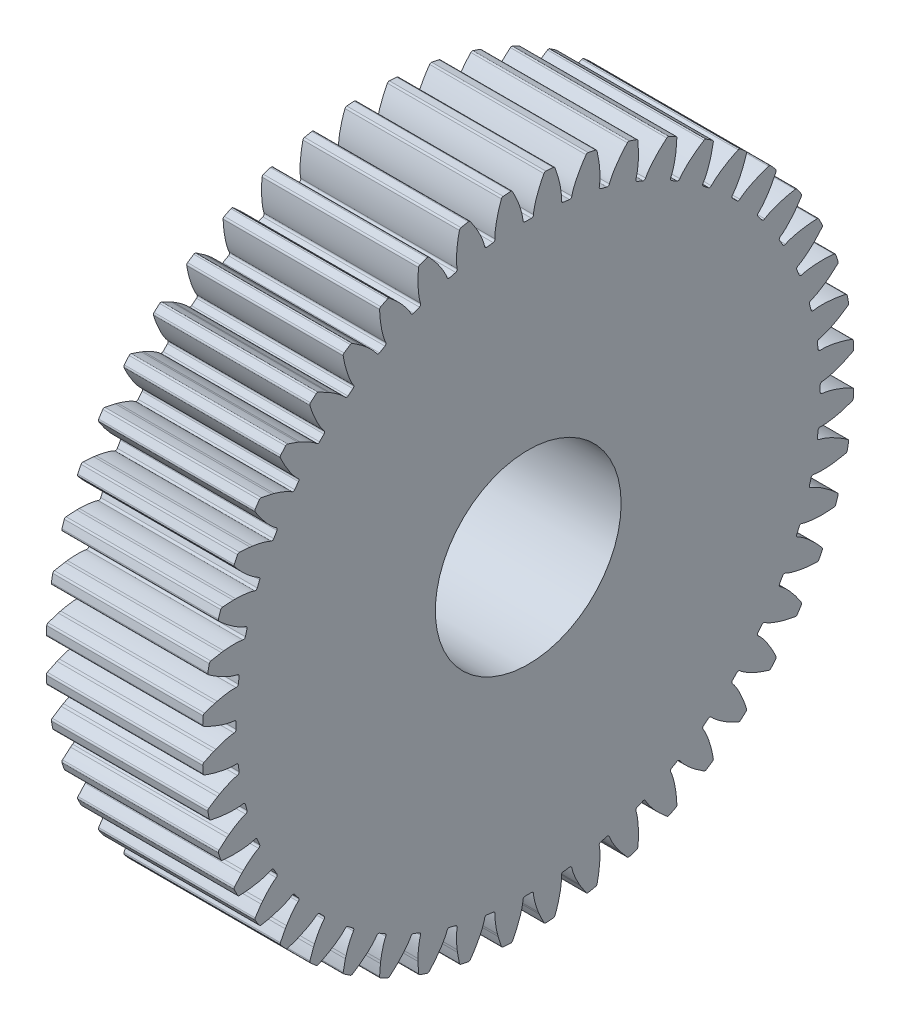
SolidWorks part; units mm, degrees
ref_plane "Front Plane" through (0, 0, 0) normal (1, 0, 0) x (0, 1, 0)
ref_plane "Top Plane" through (0, 0, 0) normal (0, 0, 1) x (0, 1, 0)
ref_plane "Right Plane" through (0, 0, 0) normal (0, 1, 0) x (-1, 0, 0)
sketch "Sketch2" plane through (0, 0, 0) normal (1, 0, 0) x (0, 1, 0)
  circle A0 centre (0, 0) radius 7.5406
  circle A1 centre (0, 0) radius 26.4583
  dimension "D1" = 15.0812
  dimension "D2" = 52.9167
extrude "Gear Width Extrude" add sketch "Sketch2" along normal blind 12.7
sketch "Sketch3" plane through (0, 0, 0) normal (1, 0, 0) x (0, 1, 0)
  line L0 (-26.4583, 0) -> (26.4583, 0) construction
  line L1 (0, 26.4583) -> (0, -26.4583) construction
  line L2 (0, 0) -> (23.8644, 0.4253) construction
  line L5 (23.702, 0) -> (26.4583, 0)
  line L6 (23.8644, 0.4253) -> (23.6983, 0.4224)
  circle A0 centre (0, 0) radius 23.702 construction
  circle A1 centre (0, 0) radius 23.8682 construction
  circle A2 centre (0, 0) radius 25.4 construction
  circle A3 centre (0, 0) radius 26.4583 construction
  arc A7 (26.4253, 1.3221) -> (26.4583, 0) centre (0, 0) cw
  arc A8 (23.6983, 0.4224) -> (23.702, 0) centre (0, 0) cw
  spline S0 degree 4 poles (23.8644, 0.4253) (23.8684, 0.4254) (23.8798, 0.4259) (23.9011, 0.4272) (23.936, 0.4301) (23.9804, 0.4348) (24.0378, 0.4421) (24.1054, 0.4523) (24.1795, 0.4651) (24.2602, 0.4807) (24.3406, 0.4979) (24.4207, 0.5164) (24.5004, 0.5362) (24.5969, 0.5617) (24.7125, 0.5944) (24.8475, 0.6357) (25.0003, 0.6863) (25.1558, 0.7417) (25.3086, 0.7995) (25.4627, 0.8616) (25.6116, 0.9243) (25.766, 0.9932) (25.9084, 1.0588) (26.0675, 1.1365) (26.1958, 1.2004) (26.3647, 1.2892) (26.4643, 1.343) (26.5808, 1.4076) (26.6324, 1.437) (26.6642, 1.4552) knots 0 0 0 0 0 0.005377 0.015084 0.028532 0.04661 0.064855 0.092111 0.119476 0.146842 0.174209 0.201575 0.228941 0.256307 0.307035 0.361767 0.4165 0.471232 0.525964 0.580697 0.635429 0.690161 0.744894 0.799626 0.854358 0.909091 0.954545 1 1 1 1 1 construction
  spline S1 degree 4 poles (23.8644, 0.4253) (23.8684, 0.4254) (23.8798, 0.4259) (23.9011, 0.4272) (23.936, 0.4301) (23.9804, 0.4348) (24.0378, 0.4421) (24.1054, 0.4523) (24.1795, 0.4651) (24.2602, 0.4807) (24.3406, 0.4979) (24.4207, 0.5164) (24.5004, 0.5362) (24.5969, 0.5617) (24.7125, 0.5944) (24.8475, 0.6357) (25.0003, 0.6863) (25.1558, 0.7417) (25.3086, 0.7995) (25.4627, 0.8616) (25.6116, 0.9243) (25.766, 0.9932) (25.9084, 1.0588) (26.0675, 1.1365) (26.1958, 1.2004) (26.3281, 1.27) (26.3924, 1.3044) (26.4253, 1.3221) knots 0 0 0 0 0 0.005377 0.015084 0.028532 0.04661 0.064855 0.092111 0.119476 0.146842 0.174209 0.201575 0.228941 0.256307 0.307035 0.361767 0.4165 0.471232 0.525964 0.580697 0.635429 0.690161 0.744894 0.799626 0.854358 0.909091 0.909091 0.909091 0.909091 0.909091
  dimension "D2" = 47.7364
  dimension "D3" = 47.4041
extrude "Gear Tooth Cut" cut sketch "Sketch3" along normal through all both and the other way through all
mirror "Gear Tooth Cut Mirror" of "Gear Tooth Cut"
fillet "Tooth Fillets" radius 0.1662 4 edges at (6.35, 26.4253, 1.3221) (6.35, 26.4253, -1.3221) (6.35, 23.6983, 0.4224) (6.35, 23.6983, -0.4224)
pattern_circular "CirPattern1" count 48 over 360 of "Gear Tooth Cut", "Gear Tooth Cut Mirror", "Tooth Fillets"
sketch "Sketch4" plane through (12.7, 0, 0) normal (1, 0, 0) x (0, 1, 0)
  circle A0 centre (0, 0) radius 25.5626
  circle A2 centre (0, 0) radius 25.3721
  dimension "D1" = 51.1251
  dimension "D2" = 0.1905
split line "Split Line1"
equation "\"DP\"= 24'INPUT: Diametral Pitch"
equation "\"a_Pressure\"= 20'INPUT: Pressure Angle"
equation "\"Z\"= 48'INPUT: Number of Teeth"
equation "\"w_Face\"= 0.5'INPUT: Face Width"
equation "\"d_Bore\"= 19 / 32'INPUT: Bore Diameter"
equation "\"d_Pitch\"= \"Z\" / \"DP\"'Pitch Diameter"
equation "\"Module\"= 1 / \"DP\"'Module"
equation "\"d_Base\"= \"d_Pitch\" * cos ( \"a_Pressure\" )'Base Circle Diameter"
equation "\"Clearance\"= 0.157 / \"DP\"'Clearance"
equation "\"CP\"= pi * \"d_Pitch\" / \"Z\"'Circular Pitch"
equation "\"h_Addendum\"= 1 / \"DP\"'Addendum Depth"
equation "\"h_Dedendum\"= IIF ( \"h_deStandard\" > \"h_deMin\" , \"h_deStandard\" , \"h_deMin\" )'Dedendum Depth"
equation "\"d_Addendum\"= \"d_Pitch\" + ( 2 * \"h_Addendum\" )'Addendum (Tip) Diameter"
equation "\"d_Dedendum\"= \"d_Pitch\" - ( 2 * \"h_Dedendum\" )'Dedendum (Root) Diameter"
equation "\"a_Pitch\"= 360 / \"Z\"'Pitch Angle"
equation "\"a_Alpha\"= ( ( 180 * ( ( \"d_Pitch\" ^ 2 ) - ( \"d_Base\" ^ 2 ) ) ^ 0.5 ) / ( pi * \"d_Base\" ) ) - \"a_Pressure\"'Alpha Angle"
equation "\"a_Beta\"= ( \"a_Pitch\" / 4 ) - \"a_Alpha\"'Beta Angle"
equation "\"ICDP\"= ( ( ( \"d_Addendum\" / 2 ) ^ 2 - ( \"d_Base\" / 2 ) ^ 2 ) ^ 0.5 ) * ( 2 / \"d_Base\" )'Involute Curve Domain Parameter"
equation "\"D1@Sketch2\"=\"d_Bore\""
equation "\"D2@Sketch2\"=\"d_Addendum\""
equation "\"D1@Gear Width Extrude\" = \"w_Face\""
equation "\"D1@Sketch3\"=\"d_Pitch\""
equation "\"D2@Sketch3\"=\"d_Base\""
equation "\"D3@Sketch3\"= \"d_Dedendum\""
equation "\"D1@CirPattern1\"=\"Z\""
equation "\"D1@Tooth Fillets\"=\"Clearance\""
equation "\"h_deStandard\"= ( 1 / \"DP\" ) + \"Clearance\""
equation "\"h_deMin\"= ( \"d_Pitch\" * ( 1 - cos ( \"a_Pressure\" ) ) / 2 ) + \"Clearance\""
